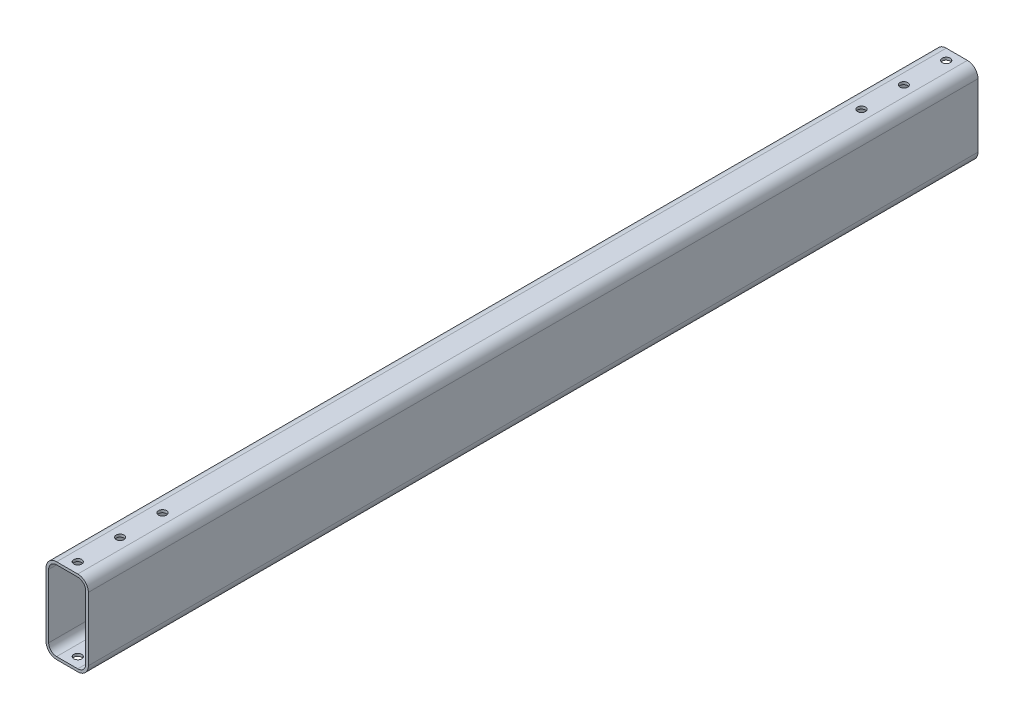
SolidWorks part; units mm, degrees
material "6061-T6 (SS)"
ref_plane "Front Plane" through (0, 0, 0) normal (0, 0, 1) x (1, 0, 0)
ref_plane "Top Plane" through (0, 0, 0) normal (0, 1, 0) x (1, 0, 0)
ref_plane "Right Plane" through (0, 0, 0) normal (1, 0, 0) x (0, 0, -1)
sketch "Sketch1" plane through (0, 0, 0) normal (0, 0, 1) x (1, 0, 0)
  line L1 (-6.35, -25.4) -> (6.35, -25.4)
  line L2 (-12.7, -19.05) -> (-12.7, 19.05)
  line L3 (-6.35, 25.4) -> (6.35, 25.4)
  line L4 (12.7, -19.05) -> (12.7, 19.05)
  line L5 (-12.7, -25.4) -> (12.7, 25.4) construction
  line L6 (-12.7, 25.4) -> (12.7, -25.4) construction
  arc A0 (-12.7, -19.05) -> (-6.35, -25.4) centre (-6.35, -19.05) ccw
  arc A1 (6.35, -25.4) -> (12.7, -19.05) centre (6.35, -19.05) ccw
  arc A2 (6.35, 25.4) -> (12.7, 19.05) centre (6.35, 19.05) cw
  arc A3 (-12.7, 19.05) -> (-6.35, 25.4) centre (-6.35, 19.05) cw
  point P0 (0, 0)
  dimension "D3" = 6.35
  dimension "D1" = 50.8
  dimension "D2" = 25.4
extrude "Extrude-Thin1" add sketch "Sketch1" along normal blind 533.4 thin thin type one direction reverse wall 1.5875
hole_wizard "3/16 (0.1875) Diameter Hole1" positions "3DSketch1" profile "Sketch3" hole size "3/16" standard "ANSI Inch" end condition through all
sketch3d "3DSketch1"
  line L1 (6.35, 25.4, 0) -> (-6.35, 25.4, 0) construction
  line L6 (0, 25.4, 533.4) -> (0, 25.4, 0) construction
  line L7 (6.35, 25.4, 533.4) -> (-6.35, 25.4, 533.4) construction
  point P57 (0, 25.4, 6.35)
  point P59 (0, 25.4, 31.75)
  point P61 (0, 25.4, 57.15)
  point P63 (0, 25.4, 501.65)
  point P65 (0, 25.4, 476.25)
  point P67 (0, 25.4, 527.05)
  dimension "D1" = 25.4
  dimension "D2" = 25.4
  dimension "D3" = 6.35
  dimension "D4" = 25.4
  dimension "D5" = 25.4
  dimension "D6" = 6.35
sketch "Sketch3" plane through (0, 25.4, 527.05) normal (1, 0, 0) x (0, 0, 1)
  line L0 (0, 0) -> (0, 50.8)
  line L1 (0, 50.8) -> (2.3812, 50.8)
  line L2 (2.3812, 50.8) -> (2.3812, 0)
  line L5 (2.3812, 0) -> (0, 0)
  line L11 (0, -6.35) -> (0, 107.95) construction
  dimension "Thru Hole Dia." = 4.7625
  dimension "Thru Hole Depth" = 50.8
hole_wizard "3/16 (0.195) Diameter Hole1" positions "Sketch4" profile "Sketch5" hole size "3/16" standard "ANSI Inch" end condition up to next
sketch "Sketch4" plane through (0, -25.4, 0) normal (0, -1, 0) x (-1, 0, 0)
  point P0 (-6.331, -114.3163)
  point P3 (0.2817, -139.6492)
  point P6 (-5.805, -165.1136)
  point P9 (0.8077, -190.4465)
  point P15 (-3.175, -419.1)
  point P18 (2.9117, -393.6356)
  point P21 (-3.701, -368.3027)
  point P24 (2.3857, -342.8383)
sketch "Sketch5" plane through (6.331, -25.4, 114.3163) normal (1, 0, 0) x (0, 0, -1)
  line L0 (0, 0) -> (0, 1.5875)
  line L1 (0, 1.5875) -> (2.4765, 1.5875)
  line L2 (2.4765, 1.5875) -> (2.4765, 0)
  line L5 (2.4765, 0) -> (0, 0)
  line L11 (0, -6.35) -> (0, 107.95) construction
  dimension "Thru Hole Dia." = 4.953
  dimension "Thru Hole Depth" = 1.5875
